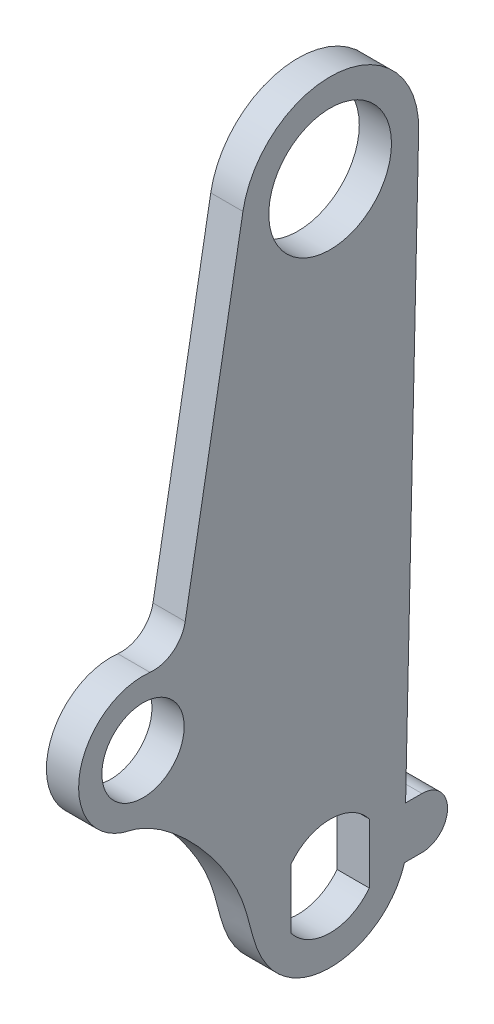
SolidWorks part; units mm, degrees
ref_plane "Front Plane" through (0, 0, 0) normal (0, 0, 1) x (1, 0, 0)
ref_plane "Top Plane" through (0, 0, 0) normal (0, 1, 0) x (1, 0, 0)
ref_plane "Right Plane" through (0, 0, 0) normal (1, 0, 0) x (0, 0, -1)
sketch "Sketch1" plane through (0, 0, 0) normal (1, 0, 0) x (0, 0, -1)
  line L0 (0, 0) -> (0, -47.625) construction
  line L1 (0, 0) -> (-14.7599, -31.6528) construction
  line L2 (-6.8781, 1.2175) -> (-11.434, -24.5203)
  line L3 (3.0861, -45.2631) -> (3.0861, -49.9869)
  line L4 (-3.0861, -45.2631) -> (-3.0861, -49.9869)
  line L5 (6.9832, -0.1584) -> (5.9524, -45.6057)
  line L6 (5.9524, -45.6057) -> (7.2445, -45.6057)
  line L7 (5.8608, -49.6443) -> (7.2445, -49.6443)
  circle A0 centre (0, 0) radius 4.8387
  circle A1 centre (-14.7599, -31.6528) radius 3.2461
  arc A2 (-3.0861, -49.9869) -> (3.0861, -49.9869) centre (0, -47.625) ccw
  arc A3 (-6.8781, 1.2175) -> (6.9832, -0.1584) centre (0, 0) cw
  arc A4 (-15.8353, -36.6177) -> (-14.2101, -26.6026) centre (-14.7599, -31.6528) cw
  arc A5 (3.0861, -45.2631) -> (-3.0861, -45.2631) centre (0, -47.625) ccw
  arc A6 (-11.434, -24.5203) -> (-14.2101, -26.6026) centre (-13.9351, -24.0776) cw
  arc A7 (7.2445, -45.6057) -> (7.2445, -49.6443) centre (7.2445, -47.625) cw
  spline S0 degree 3 poles (-15.8353, -36.6177) (-12.7944, -37.2763) (-7.0852, -43.3066) (-4.9787, -56.0126) (4.3192, -54.8321) (5.8608, -49.6443) knots 0 0 0 0 0.291845 0.391845 1 1 1 1
  dimension "D1" = 47.625
  dimension "D2" = 34.925
  dimension "D3" = 9.6774
  dimension "D4" = 25
  dimension "D6" = 4.0386
  dimension "D7" = 6.985
  dimension "D9" = 7.7724
  dimension "D10" = 6.1722
  dimension "D11" = 2.54
  dimension "D5" = 6.4922
  dimension "D8" = 5.08
extrude "Boss-Extrude1" add sketch "Sketch1" along normal blind 2.54
